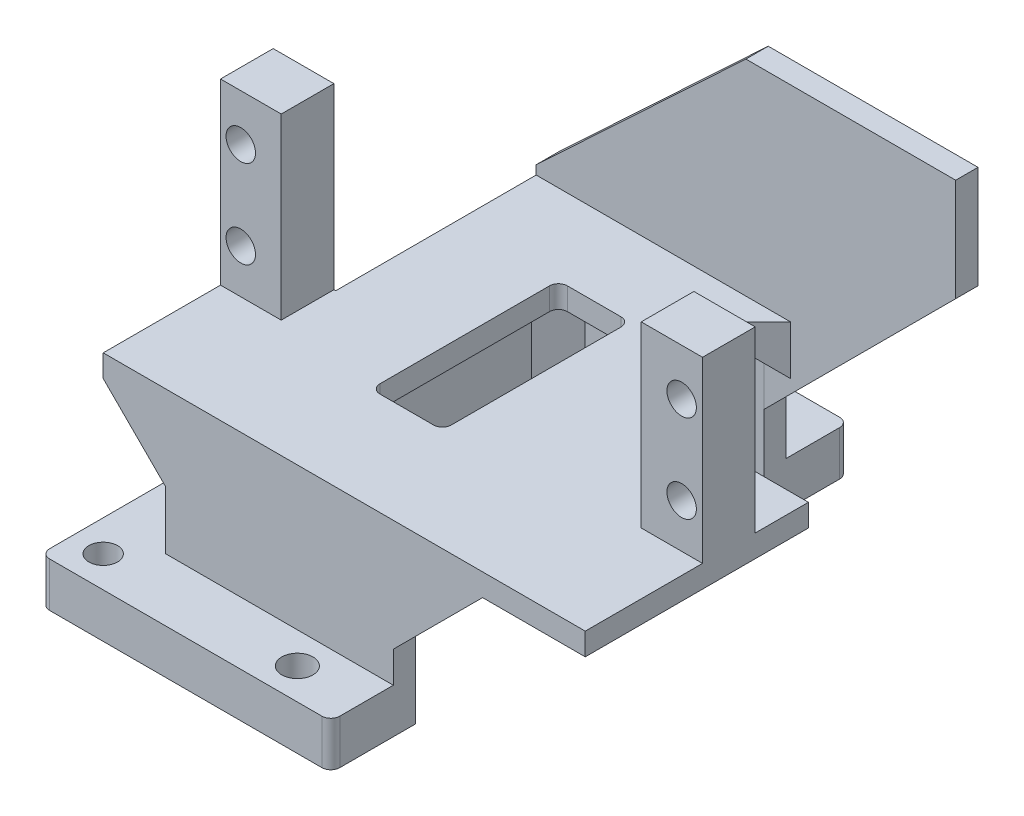
SolidWorks part; units mm, degrees
ref_plane "Front Plane" through (0, 0, 0) normal (0, 0, 1) x (1, 0, 0)
ref_plane "Top Plane" through (0, 0, 0) normal (0, 1, 0) x (1, 0, 0)
ref_plane "Right Plane" through (0, 0, 0) normal (1, 0, 0) x (0, 0, -1)
sketch "Sketch1" plane through (0, 0, 0) normal (0, 1, 0) x (1, 0, 0)
  line L0 (0, 40) -> (23, 40)
  line L1 (30, 0) -> (80, 0)
  line L2 (0, 20) -> (0, 40)
  line L3 (0, 100) -> (110, 100)
  line L4 (110, 20) -> (110, 40)
  line L5 (23, 40) -> (23, 79)
  line L6 (23, 79) -> (0, 79)
  line L7 (110, 79) -> (87, 79)
  line L8 (87, 79) -> (87, 40)
  line L9 (87, 40) -> (110, 40)
  line L10 (0, 79) -> (0, 100)
  line L11 (110, 79) -> (110, 100)
  line L12 (0, 20) -> (30, 0)
  line L13 (110, 20) -> (80, 0)
  point P0 (55, 0)
  dimension "D1" = 100
  dimension "D2" = 110
  dimension "23" = 23
  dimension "D4" = 40
  dimension "20" = 23
  dimension "D5" = 39
  dimension "40" = 40
extrude "Boss-Extrude1" add sketch "Sketch1" along normal blind 3.5
sketch "Sketch2" plane through (0, 3.5, 0) normal (0, 1, 0) x (1, 0, 0)
  line L0 (0, 79) -> (23, 79)
  line L1 (23, 79) -> (23, 40)
  line L2 (23, 40) -> (0, 40)
  line L3 (0, 40) -> (0, 37.5)
  line L4 (0, 40) -> (0, 20) construction
  line L5 (0, 37.5) -> (25.5, 37.5)
  line L6 (25.5, 37.5) -> (25.5, 81.5)
  line L7 (25.5, 81.5) -> (0, 81.5)
  line L8 (0, 100) -> (0, 79) construction
  line L9 (0, 81.5) -> (0, 79)
  line L10 (110, 81.5) -> (84.5, 81.5)
  line L11 (110, 79) -> (110, 100) construction
  line L12 (84.5, 81.5) -> (84.5, 37.5)
  line L13 (84.5, 37.5) -> (110, 37.5)
  line L14 (110, 20) -> (110, 40) construction
  line L15 (110, 37.5) -> (110, 40)
  line L16 (110, 40) -> (87, 40)
  line L17 (87, 40) -> (87, 79)
  line L18 (110, 81.5) -> (110, 79)
  line L19 (110, 79) -> (87, 79)
  dimension "D1" = 2.5
  dimension "3" = 2.5
  dimension "D2" = 2.5
  dimension "D3" = 2.5
  dimension "D4" = 2.5
  dimension "D5" = 2.5
extrude "Boss-Extrude2" add sketch "Sketch2" along normal blind 21
sketch "Sketch3" plane through (0, 24.5, 0) normal (0, 1, 0) x (1, 0, 0)
  line L1 (23, 79) -> (0, 79)
  line L2 (23, 79) -> (23, 40)
  line L3 (23, 40) -> (0, 40)
  line L4 (0, 79) -> (0, 40)
  line L5 (87, 79) -> (110, 79)
  line L6 (87, 79) -> (87, 40)
  line L7 (87, 40) -> (110, 40)
  line L8 (110, 79) -> (110, 40)
extrude "Boss-Extrude3" add sketch "Sketch3" against normal blind 2.5
sketch "Sketch5" plane through (0, 24.5, 0) normal (0, 1, 0) x (1, 0, 0)
  line L0 (55, 100) -> (55, 0) construction
  line L1 (110, 100) -> (0, 100) construction
  line L2 (30, 0) -> (80, 0) construction
  line L3 (110, 62.5) -> (131.5, 62.5)
  line L4 (0, 37.5) -> (-21.5, 37.5)
  line L5 (0, 37.5) -> (0, 62.5)
  line L6 (0, 62.5) -> (-21.5, 62.5)
  line L7 (-21.5, 37.5) -> (-21.5, 62.5)
  line L8 (131.5, 37.5) -> (131.5, 62.5)
  line L9 (110, 37.5) -> (131.5, 37.5)
  line L10 (110, 37.5) -> (110, 62.5)
  line L13 (25.5, 56.54) -> (25.5, 37.5)
  line L14 (25.5, 37.5) -> (32.57, 37.5)
  line L15 (32.57, 56.54) -> (32.57, 37.5)
  line L18 (84.5, 56.54) -> (84.5, 37.5)
  line L19 (84.5, 37.5) -> (77.43, 37.5)
  line L20 (77.43, 56.54) -> (77.43, 37.5)
  line L21 (25.5, 37.5) -> (25.5, 56.54) construction
  line L23 (25.5, 56.54) -> (32.57, 56.54)
  line L24 (77.43, 56.54) -> (84.5, 56.54) construction
  line L25 (84.5, 56.54) -> (77.43, 56.54)
  dimension "D1" = 21.5
  dimension "D2" = 25
extrude "Boss-Extrude5" add sketch "Sketch5" against normal blind 2.5
sketch "Sketch6" plane through (0, 24.5, 0) normal (0, 1, 0) x (1, 0, 0)
  line L0 (55, 100) -> (55, 0) construction
  line L1 (110, 100) -> (0, 100) construction
  line L2 (30, 0) -> (80, 0) construction
  line L3 (32.57, 37.5) -> (32.57, 56.54) construction
  line L4 (25.5, 56.54) -> (32.57, 56.54)
  line L5 (25.5, 56.54) -> (25.5, 50.64)
  line L6 (25.5, 50.64) -> (32.57, 50.64)
  line L7 (32.57, 56.54) -> (32.57, 50.64)
  line L8 (84.5, 50.64) -> (77.43, 50.64)
  line L9 (77.43, 56.54) -> (77.43, 50.64)
  line L10 (84.5, 56.54) -> (77.43, 56.54)
  line L11 (84.5, 56.54) -> (84.5, 50.64)
  line L12 (-21.5, 62.5) -> (-21.5, 37.5) construction
  line L13 (-21.5, 56.54) -> (-14.43, 56.54)
  line L14 (-21.5, 56.54) -> (-21.5, 50.64)
  line L15 (-21.5, 50.64) -> (-14.43, 50.64)
  line L16 (-14.43, 56.54) -> (-14.43, 50.64)
  line L17 (131.5, 50.64) -> (124.43, 50.64)
  line L18 (124.43, 56.54) -> (124.43, 50.64)
  line L19 (131.5, 56.54) -> (124.43, 56.54)
  line L20 (131.5, 56.54) -> (131.5, 50.64)
  dimension "D1" = 5.9
  dimension "D2" = 7.07
  dimension "D3" = 7.07
extrude "Boss-Extrude6" add sketch "Sketch6" along normal blind 20
sketch "Sketch7" plane through (0, 24.5, 0) normal (0, 1, 0) x (1, 0, 0)
  line L0 (55, 100) -> (55, 0) construction
  line L1 (110, 100) -> (0, 100) construction
  line L2 (30, 0) -> (80, 0) construction
  line L3 (25.5, 56.54) -> (25.5, 81.5) construction
  line L4 (0, 81.5) -> (25.5, 81.5)
  line L6 (0, 79) -> (25.5, 79)
  line L7 (25.5, 81.5) -> (25.5, 79)
  line L8 (110, 79) -> (84.5, 79)
  line L9 (84.5, 81.5) -> (84.5, 79)
  line L10 (110, 81.5) -> (84.5, 81.5)
  line L13 (0, 79) -> (-21.5, 79)
  line L15 (0, 81.5) -> (-21.5, 81.5)
  line L16 (-21.5, 79) -> (-21.5, 81.5)
  line L18 (110, 79) -> (131.5, 79)
  line L20 (110, 81.5) -> (131.5, 81.5)
  line L21 (131.5, 79) -> (131.5, 81.5)
  dimension "D1" = 2.5
extrude "Boss-Extrude7" add sketch "Sketch7" along normal blind 23
fillet "Fillet1" radius 10 4 edges at (0, 22, -38.75) (110, 22, -38.75) (0, 24.5, -80.25) (110, 24.5, -80.25) profile chamfer
sketch "Sketch9" plane through (0, 0, -81.5) normal (0, 0, -1) x (-1, 0, 0)
  line L0 (-131.5, 47.5) -> (-84.5, 47.5) construction
  line L3 (-131.5, 47.5) -> (-131.5, 24.5) construction
  line L4 (-55, 0) -> (-55, 48.0721) construction
  line L5 (-110, 0) -> (0, 0) construction
  circle A0 centre (-114.55, 34.35) radius 2.475
  circle A1 centre (4.55, 34.35) radius 2.475
  point P6 (-114.55, 34.35)
  dimension "D2" = 4.95
  dimension "D1" = 13.15
  dimension "D3" = 16.95
extrude "Boss-Extrude8" add sketch "Sketch9" along normal blind 9
fillet "Fillet2" radius 0.5 2 edges at (-2.075, 34.35, -90.5) (112.075, 34.35, -90.5)
sketch "Sketch10" plane through (0, 0, -50.64) normal (0, 0, 1) x (1, 0, 0)
  line L0 (55, 0) -> (55, 49.7444) construction
  line L1 (30, 0) -> (80, 0) construction
  line L2 (129.16, 44.5) -> (129.16, 24.5) construction
  line L3 (124.43, 44.5) -> (131.5, 44.5) construction
  line L4 (124.43, 24.5) -> (131.5, 24.5) construction
  line L5 (131.5, 44.5) -> (131.5, 24.5) construction
  line L6 (79.77, 44.5) -> (79.77, 24.5) construction
  line L7 (77.43, 44.5) -> (84.5, 44.5) construction
  line L8 (77.43, 24.5) -> (84.5, 24.5) construction
  line L9 (77.43, 44.5) -> (77.43, 24.5) construction
  circle A0 centre (129.16, 39.27) radius 1.65
  circle A1 centre (129.16, 29.43) radius 1.65
  circle A2 centre (79.77, 39.27) radius 1.65
  circle A3 centre (79.77, 29.43) radius 1.65
  circle A4 centre (-19.16, 29.43) radius 1.65
  circle A5 centre (-19.16, 39.27) radius 1.65
  circle A6 centre (30.23, 39.27) radius 1.65
  circle A7 centre (30.23, 29.43) radius 1.65
  dimension "D3" = 5.23
  dimension "D4" = 3.3
  dimension "D5" = 4.93
  dimension "D6" = 3.3
  dimension "D7" = 3.3
  dimension "D8" = 3.3
  dimension "D1" = 2.34
  dimension "D2" = 2.34
extrude "Cut-Extrude1" cut sketch "Sketch10" against normal blind 9
sketch "Sketch11" plane through (0, 0, -50.64) normal (0, 0, 1) x (1, 0, 0)
  line L0 (-21.5, 24.5) -> (-14.43, 24.5) construction
  line L1 (-14.43, 44.5) -> (-14.63, 44.5)
  line L2 (-14.43, 44.5) -> (-14.43, 24.5)
  line L3 (-14.43, 24.5) -> (-14.63, 24.5)
  line L4 (-14.63, 44.5) -> (-14.63, 24.5)
  line L5 (25.5, 24.5) -> (32.57, 24.5) construction
  line L6 (25.5, 44.5) -> (25.7, 44.5)
  line L7 (25.5, 44.5) -> (25.5, 24.5)
  line L8 (25.5, 24.5) -> (25.7, 24.5)
  line L9 (25.7, 44.5) -> (25.7, 24.5)
  line L10 (55, 3.5) -> (55, 47.4628) construction
  line L11 (30, 3.5) -> (80, 3.5) construction
  line L12 (84.5, 24.5) -> (84.3, 24.5)
  line L13 (84.3, 44.5) -> (84.3, 24.5)
  line L14 (84.5, 44.5) -> (84.3, 44.5)
  line L15 (84.5, 44.5) -> (84.5, 24.5)
  line L16 (124.43, 24.5) -> (124.63, 24.5)
  line L17 (124.63, 44.5) -> (124.63, 24.5)
  line L18 (124.43, 44.5) -> (124.63, 44.5)
  line L19 (124.43, 44.5) -> (124.43, 24.5)
  dimension "D1" = 0.2
  dimension "D2" = 0.2
extrude "Cut-Extrude2" cut sketch "Sketch11" against normal blind 9
sketch "Sketch12" plane through (0, 0, -81.5) normal (0, 0, -1) x (-1, 0, 0)
  line L0 (-108, 47.5) -> (-84.5, 25.5)
  line L1 (-131.5, 47.5) -> (-84.5, 47.5) construction
  line L2 (-84.5, 47.5) -> (-84.5, 3.5) construction
  line L3 (-84.5, 25.5) -> (-84.5, 47.5)
  line L4 (-84.5, 47.5) -> (-108, 47.5)
  line L5 (-55, 3.5) -> (-55, 47.5) construction
  line L6 (-110, 3.5) -> (0, 3.5) construction
  line L7 (-25.5, 25.5) -> (-25.5, 47.5)
  line L8 (-2, 47.5) -> (-25.5, 25.5)
  line L9 (-25.5, 47.5) -> (-2, 47.5)
  line L10 (-120, 24.5) -> (-131.5, 36)
  line L11 (-131.5, 47.5) -> (-131.5, 24.5) construction
  line L12 (-131.5, 36) -> (-131.5, 24.5)
  line L13 (-131.5, 24.5) -> (-120, 24.5)
  line L14 (10, 24.5) -> (21.5, 36)
  line L15 (21.5, 47.5) -> (21.5, 24.5) construction
  line L16 (21.5, 36) -> (21.5, 24.5)
  line L17 (21.5, 24.5) -> (10, 24.5)
extrude "Cut-Extrude3" cut sketch "Sketch12" against normal blind 9
fillet "Fillet3" radius 3 2 edges at (110, 23.25, -62.5) (0, 23.25, -62.5) profile chamfer
sketch "Sketch13" plane through (0, 3.5, 0) normal (0, 1, 0) x (1, 0, 0)
  line L0 (55, 100) -> (55, 0) construction
  line L1 (110, 100) -> (0, 100) construction
  line L2 (30, 0) -> (80, 0) construction
  line L3 (0, 30.5) -> (32.5, 30.5)
  line L4 (0, 37.5) -> (0, 20) construction
  line L5 (32.5, 30.5) -> (32.5, 88.5)
  line L6 (32.5, 88.5) -> (0, 88.5)
  line L7 (0, 100) -> (0, 81.5) construction
  line L8 (0, 88.5) -> (0, 81.5)
  line L9 (0, 81.5) -> (25.5, 81.5)
  line L10 (25.5, 81.5) -> (25.5, 37.5)
  line L11 (25.5, 37.5) -> (0, 37.5)
  line L12 (0, 37.5) -> (0, 30.5)
  line L13 (84.5, 37.5) -> (110, 37.5)
  line L14 (84.5, 81.5) -> (84.5, 37.5)
  line L15 (110, 81.5) -> (84.5, 81.5)
  line L16 (110, 88.5) -> (110, 81.5)
  line L17 (77.5, 88.5) -> (110, 88.5)
  line L18 (77.5, 30.5) -> (77.5, 88.5)
  line L19 (110, 30.5) -> (77.5, 30.5)
  line L20 (110, 37.5) -> (110, 30.5)
  dimension "D1" = 7
  dimension "D2" = 7
  dimension "D3" = 7
extrude "Boss-Extrude9" add sketch "Sketch13" along normal blind 5
sketch "Sketch14" plane through (0, 8.5, 0) normal (0, 1, 0) x (1, 0, 0)
  line L0 (55, 100) -> (55, 0) construction
  line L1 (110, 100) -> (0, 100) construction
  line L2 (30, 0) -> (80, 0) construction
  line L3 (0, 85) -> (29, 85) construction
  line L4 (0, 88.5) -> (0, 81.5) construction
  line L5 (29, 85) -> (29, 34) construction
  line L6 (29, 34) -> (0, 34) construction
  line L7 (0, 37.5) -> (0, 30.5) construction
  line L8 (32.5, 30.5) -> (32.5, 88.5) construction
  circle A0 centre (7.25, 34) radius 1.7478
  circle A3 centre (7.25, 85) radius 1.6
  circle A5 centre (29, 34) radius 1.6
  circle A6 centre (29, 59.5) radius 1.6
  circle A7 centre (29, 85) radius 1.6
  circle A8 centre (81, 34) radius 1.6
  circle A9 centre (102.75, 34) radius 1.7478
  circle A10 centre (81, 59.5) radius 1.6
  circle A11 centre (81, 85) radius 1.6
  circle A12 centre (102.75, 85) radius 1.6
  dimension "D2" = 3.2
  dimension "D3" = 7.25
  dimension "D4" = 3.2
  dimension "D6" = 3.2
  dimension "D7" = 7.25
  dimension "3.2" = 3.2
  dimension "D1" = 3.5
extrude "Cut-Extrude4" cut sketch "Sketch14" against normal blind 15
sketch "Sketch15" plane through (0, 0, -100) normal (0, 0, -1) x (-1, 0, 0)
  line L1 (-110, 3.5) -> (0, 3.5)
  line L2 (-110, 3.5) -> (-110, 0)
  line L3 (-110, 0) -> (0, 0)
  line L4 (0, 3.5) -> (0, 0)
  line L5 (21.5, 47.5) -> (-77.5, 47.5)
  line L6 (21.5, 47.5) -> (21.5, 3.5)
  line L7 (21.5, 3.5) -> (-77.5, 3.5)
  line L8 (-77.5, 47.5) -> (-77.5, 3.5)
  line M3 (0, 3.5) -> (-110, 3.5)
extrude "Cut-Extrude5" cut sketch "Sketch15" against normal blind 150 contours L5 L8 L7 L6 M3 | L3 L4 L1 L2 region at (28, 25.5, -100)
fillet "Fillet4" radius 7 1 edges at (84.5, 22, -47.02) profile chamfer
fillet "Fillet5" radius 3 3 edges at (98.5, 22, -79) (103.5, 22, -40) (87, 22, -59.5) profile chamfer
fillet "Fillet6" radius 3 1 edges at (110, 21.75, -79) profile chamfer
sketch "Sketch17" plane through (0, 22, 0) normal (0, -1, 0) x (1, 0, 0)
  line L0 (90, -43) -> (90, -76) construction
  line L1 (96, -49) -> (104, -49)
  line L2 (96, -49) -> (96, -70)
  line L3 (96, -70) -> (104, -70)
  line L4 (104, -49) -> (104, -70)
  line L5 (120, -43) -> (90, -43) construction
  line L6 (110, -65.5) -> (110, -76) construction
  line L7 (90, -76) -> (110, -76) construction
  dimension "D1" = 6
  dimension "D2" = 6
  dimension "D3" = 6
  dimension "D4" = 6
extrude "Cut-Extrude6" cut sketch "Sketch17" against normal blind 150
fillet "Fillet7" radius 1 4 edges at (104, 23.25, -70) (104, 23.25, -49) (96, 23.25, -49) (96, 23.25, -70)
fillet "Fillet8" radius 1 4 edges at (110, 6, -88.5) (77.5, 6, -88.5) (77.5, 6, -30.5) (110, 6, -30.5)
fillet "Fillet9" radius 3 2 edges at (87, 11.25, -79) (87, 11.25, -40) profile chamfer
